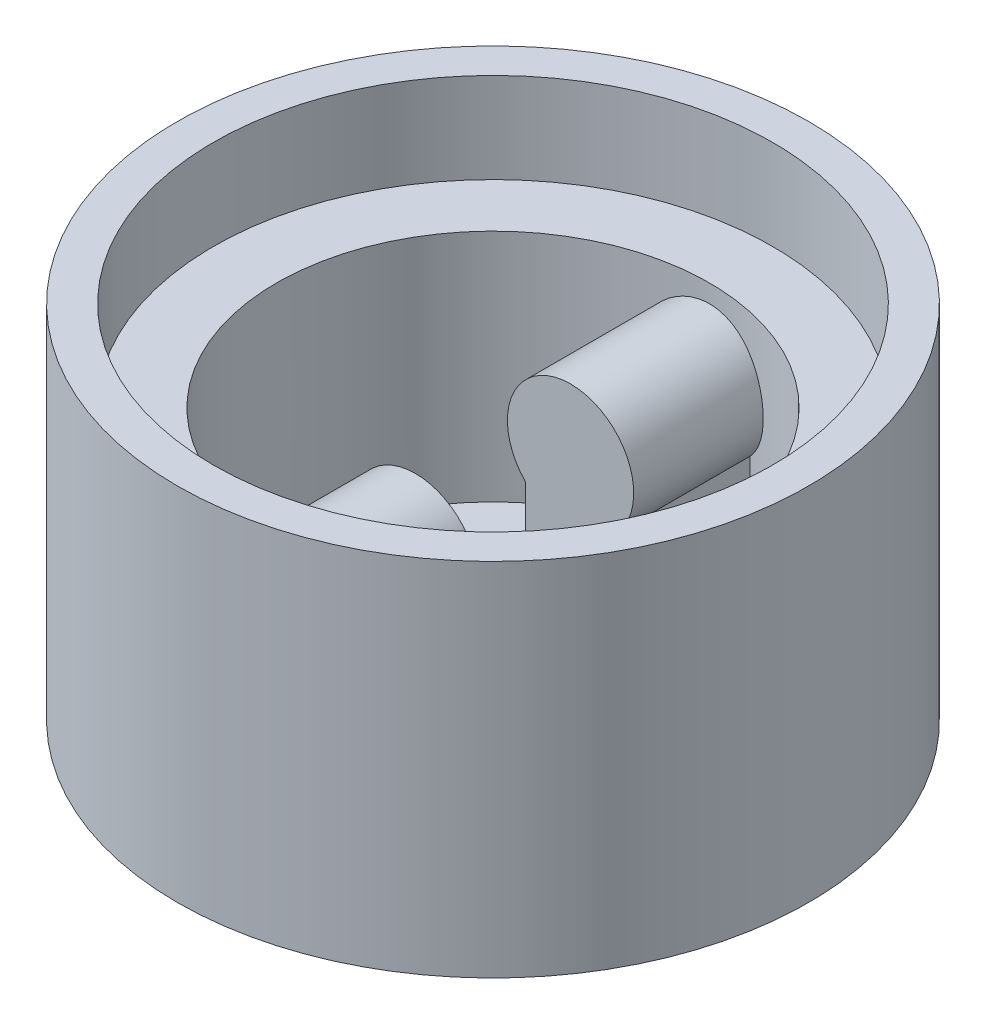
SolidWorks part; units mm, degrees
material "ABS"
ref_plane "Front Plane" through (0, 0, 0) normal (0, 0, 1) x (1, 0, 0)
ref_plane "Top Plane" through (0, 0, 0) normal (0, 1, 0) x (1, 0, 0)
ref_plane "Right Plane" through (0, 0, 0) normal (1, 0, 0) x (0, 0, -1)
sketch "Sketch1" plane through (0, 0, 0) normal (0, 1, 0) x (1, 0, 0)
  circle A0 centre (0, 0) radius 17.5
  dimension "D1" = 35
extrude "Boss-Extrude1" add sketch "Sketch1" along normal blind 20
sketch "Sketch2" plane through (0, 20, 0) normal (0, 1, 0) x (1, 0, 0)
  circle A0 centre (0, 0) radius 17.5 construction
  circle A1 centre (0, 0) radius 17.5
  circle A2 centre (0, 0) radius 12
  circle A3 centre (0, 0) radius 15.5
  dimension "D1" = 24
  dimension "D2" = 2
extrude "Cut-Extrude1" cut sketch "Sketch2" against normal offset from surface (18 mm away) 2 contours A2 region at (0, 20, 0) up to face at (0, 0, 17.5)
extrude "Cut-Extrude2" cut sketch "Sketch2<3>" against normal blind 5 contours A3 A2 region at (-15.0616, 20, 0)
sketch "Sketch2<3>" plane through (0, 20, 0) normal (0, 1, 0) x (1, 0, 0) same geometry as "Sketch2"
sketch "Sketch3" plane through (0, 0, 0) normal (0, 0, 1) x (1, 0, 0)
  line L0 (-2.5, 8.0505) -> (-2.5, 2)
  line L1 (12, 2) -> (-12, 2) construction
  line L2 (2.5, 8.0505) -> (2.5, 2)
  line L4 (-2.5, 2) -> (2.5, 2)
  arc A0 (2.5, 8.0505) -> (-2.5, 8.0505) centre (0, 10.5) ccw
  dimension "D1" = 7
  dimension "D3" = 12
  dimension "D2" = 5
extrude "Boss-Extrude2" add sketch "Sketch3" along normal up to next and the other way up to next
sketch "Sketch5" plane through (0, 20, 0) normal (0, 1, 0) x (1, 0, 0)
  line L0 (3.5, -11.4783) -> (3.5, 11.4783) construction
  line L1 (-3.5, -4.3) -> (3.5, -4.3)
  line L2 (-3.5, -4.3) -> (-3.5, 4.3)
  line L3 (-3.5, 4.3) -> (3.5, 4.3)
  line L4 (3.5, -4.3) -> (3.5, 4.3)
  line L5 (-3.5, -4.3) -> (3.5, 4.3) construction
  line L6 (-3.5, 4.3) -> (3.5, -4.3) construction
  point P0 (0, 0)
  dimension "D1" = 8.6
extrude "Cut-Extrude3" cut sketch "Sketch5" against normal up to surface (18 mm away) up to face at (-7.25, 2, 0)
hole_wizard "Ø4.0mm Dowel Hole1" positions "3DSketch1" profile "Sketch7" hole size "Ø4.0" standard "ANSI Metric" end condition through all
sketch3d "3DSketch1"
  point P0 (0, 0, 0)
  point P3 (0, 2, 0)
sketch "Sketch7" plane through (0, 2, 0) normal (1, 0, 0) x (0, 0, 1)
  line L0 (0, 0) -> (0, 2)
  line L1 (0, 2) -> (2, 2)
  line L2 (2, 2) -> (2, 0)
  line L5 (2, 0) -> (0, 0)
  line L11 (0, -6.35) -> (0, 107.95) construction
  dimension "Thru Hole Dia." = 4
  dimension "Thru Hole Depth" = 2
